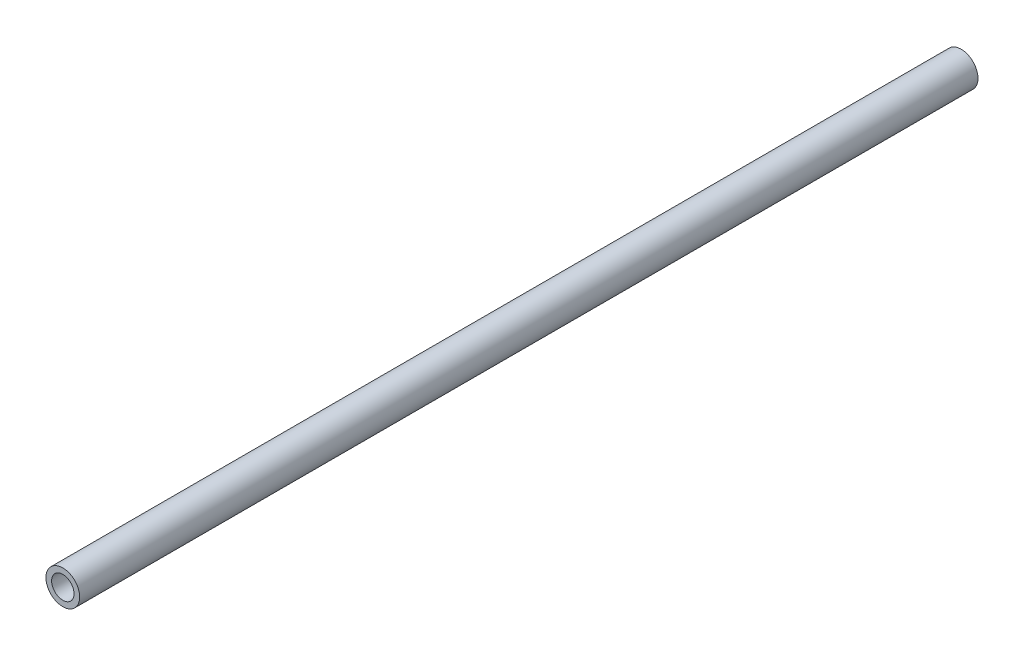
SolidWorks part; units mm, degrees
ref_plane "Front Plane" through (0, 0, 0) normal (0, 0, 1) x (1, 0, 0)
ref_plane "Top Plane" through (0, 0, 0) normal (0, 1, 0) x (1, 0, 0)
ref_plane "Right Plane" through (0, 0, 0) normal (1, 0, 0) x (0, 0, -1)
sketch "Sketch2" plane through (0, 0, 0) normal (0, 0, 1) x (1, 0, 0)
  circle A0 centre (0, 0) radius 7.5
  circle A1 centre (0, 0) radius 5
extrude "Boss-Extrude1" add sketch "Sketch2" along normal blind 400
